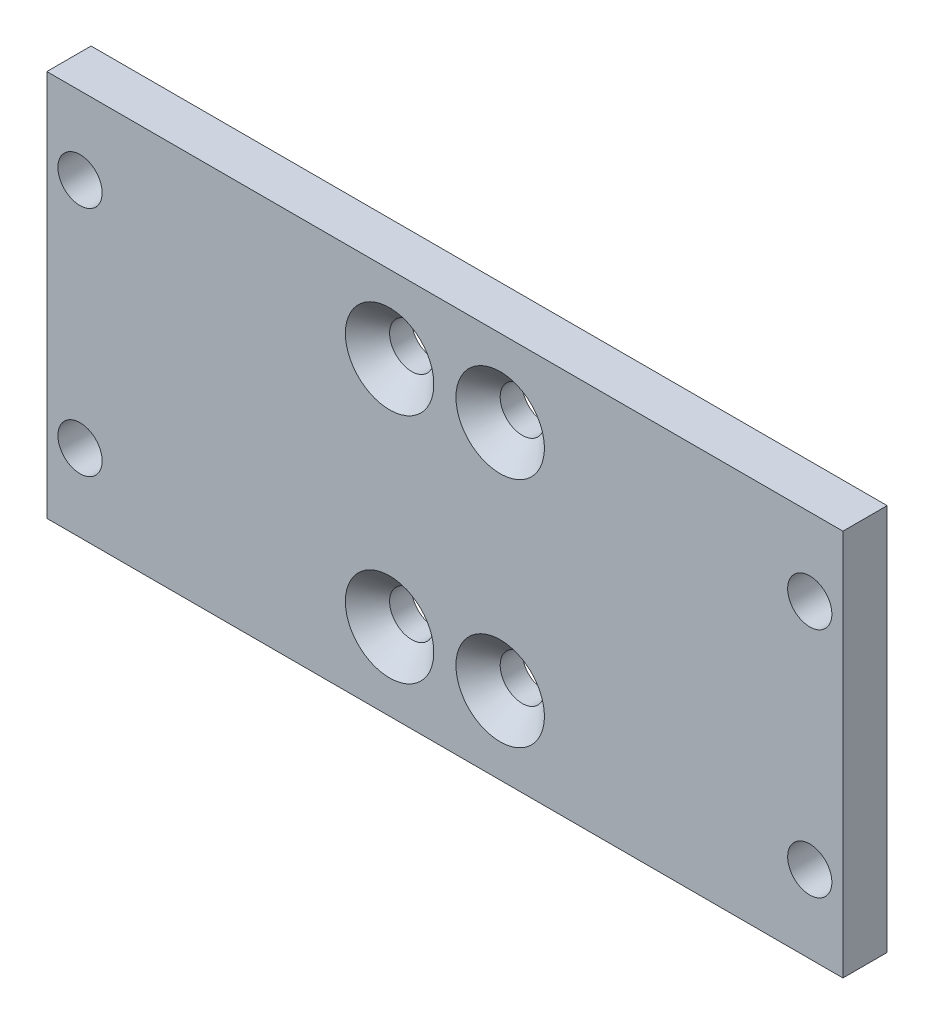
SolidWorks part; units mm, degrees
ref_plane "Front Plane" through (0, 0, 0) normal (0, 0, 1) x (1, 0, 0)
ref_plane "Top Plane" through (0, 0, 0) normal (0, 1, 0) x (1, 0, 0)
ref_plane "Right Plane" through (0, 0, 0) normal (1, 0, 0) x (0, 0, -1)
sketch "Sketch1" plane through (0, 0, 0) normal (0, 0, 1) x (1, 0, 0)
  line L0 (-42.8772, -12.649) -> (23.1228, -12.649) construction
  line L2 (-45.8772, -30.149) -> (26.1228, -30.149)
  line L3 (-45.8772, -30.149) -> (-45.8772, 4.851)
  line L4 (-45.8772, 4.851) -> (26.1228, 4.851)
  line L5 (26.1228, -30.149) -> (26.1228, 4.851)
  line L6 (-45.8772, -30.149) -> (26.1228, 4.851) construction
  line L7 (-45.8772, 4.851) -> (26.1228, -30.149) construction
  circle A0 centre (-14.8772, -2.149) radius 2
  circle A1 centre (-4.8772, -2.149) radius 2
  circle A2 centre (-42.8772, -2.149) radius 2
  circle A3 centre (23.1228, -2.149) radius 2
  circle A4 centre (23.1228, -23.149) radius 2
  circle A5 centre (-42.8772, -23.149) radius 2
  circle A6 centre (-4.8772, -23.149) radius 2
  circle A7 centre (-14.8772, -23.149) radius 2
  point P18 (-9.8772, -12.649)
  dimension "D1" = 10
  dimension "D2" = 28
  dimension "D3" = 28
  dimension "D4" = 10.5
  dimension "D5" = 35
  dimension "D6" = 72
extrude "Boss-Extrude1" add sketch "Sketch1" along normal blind 4
chamfer "Chamfer1" distance 2 angle 45 4 edges at (-16.8772, -23.149, 4) (-6.8772, -23.149, 4) (-2.8772, -2.149, 4) (-12.8772, -2.149, 4)
